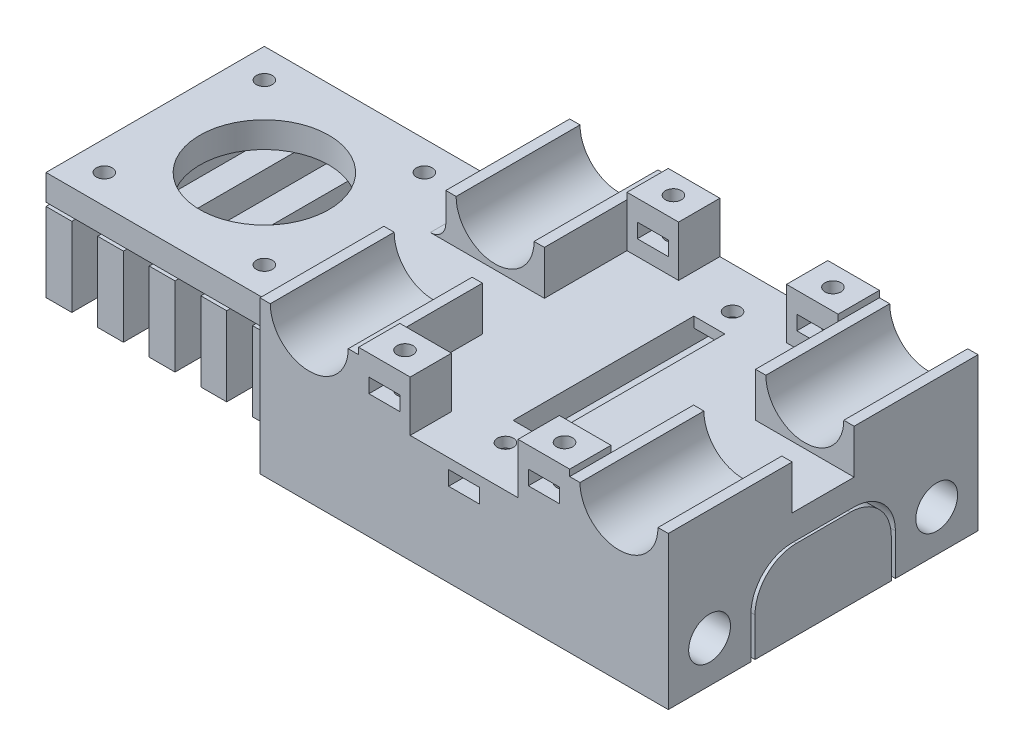
SolidWorks part; units mm, degrees
note: The reader was unsure of these and kept them because the rebuilt part matched: shared geometry of "Sketch14<3>".
ref_plane "Front Plane" through (0, 0, 0) normal (0, 0, 1) x (1, 0, 0)
ref_plane "Top Plane" through (0, 0, 0) normal (0, 1, 0) x (1, 0, 0)
ref_plane "Right Plane" through (0, 0, 0) normal (1, 0, 0) x (0, 0, -1)
sketch "Sketch1" plane through (0, 0, 0) normal (0, 1, 0) x (1, 0, 0)
  line L1 (-39.55, 30) -> (39.55, 30)
  line L2 (-39.55, 30) -> (-39.55, -30)
  line L3 (-39.55, -30) -> (39.55, -30)
  line L4 (39.55, 30) -> (39.55, -30)
  dimension "D1" = 60
  dimension "D2" = 79.1
  dimension "D3" = 39.55
  dimension "D4" = 30
extrude "Boss-Extrude1" add sketch "Sketch1" along normal blind 5
sketch "Sketch2" plane through (0, 0, 30) normal (0, 0, 1) x (1, 0, 0)
  line L0 (-39.55, 5) -> (39.55, 5) construction
  line L1 (-39.55, 5) -> (-20.45, 5)
  line L2 (-39.55, 5) -> (-39.55, 13.55)
  line L3 (-39.55, 13.55) -> (-20.45, 13.55)
  line L4 (-20.45, 5) -> (-20.45, 13.55)
  circle A0 centre (-30, 13.55) radius 7.55
  line M3 (39.55, 5) -> (-39.55, 5)
  dimension "D3" = 15.1
  dimension "D1" = 19.1
  dimension "D2" = 8.55
  dimension "D4" = 30
extrude "Boss-Extrude2" add sketch "Sketch2" against normal blind 24 contours A0 L3 L2 L4 M3
mirror "Mirror1" about plane through (0, 0, 0) normal (0, 0, 1) of "Boss-Extrude2"
mirror "Mirror2" about plane through (0, 0, 0) normal (1, 0, 0) of "Mirror1", "Boss-Extrude2"
ref_plane "Plane1" through (-30, 0, 0) normal (-1, 0, 0) x (0, 0, 1)
ref_plane "Plane2" through (-22.275, 22.275, 0) normal (-0.7071, 0.7071, 0) x (0.7071, 0.7071, 0)
sketch "Sketch3" plane through (-22.275, 22.275, 0) normal (-0.7071, 0.7071, 0) x (0.7071, 0.7071, 0)
  line L0 (-27.9661, -30) -> (-18.3848, -30) construction
  line L1 (-24.4305, -6) -> (-24.4305, 6) construction
  circle A0 centre (-27.9305, -18) radius 1.75
  dimension "D1" = 3.5
  dimension "D2" = 12
  dimension "D3" = 3.5
sketch "Sketch9" plane through (0, 0, 30) normal (0, 0, 1) x (1, 0, 0)
  line L1 (-20.45, 5) -> (-10.45, 5)
  line L2 (-20.45, 5) -> (-20.45, 14.8)
  line L3 (-20.45, 14.8) -> (-10.45, 14.8)
  line L4 (-10.45, 5) -> (-10.45, 14.8)
  line L5 (-18.45, 8) -> (-12.45, 8)
  line L6 (-18.45, 8) -> (-18.45, 10.8)
  line L7 (-18.45, 10.8) -> (-12.45, 10.8)
  line L8 (-12.45, 8) -> (-12.45, 10.8)
  line M7 (20.45, 5) -> (-20.45, 5)
  line M8 (-20.45, 5) -> (-20.45, 13.55)
  dimension "D1" = 2.8
  dimension "D2" = 6
  dimension "D3" = 2
  dimension "D4" = 2
  dimension "D5" = 4
  dimension "D6" = 3
extrude "Boss-Extrude4" add sketch "Sketch9" against normal blind 8 contours L8 L4 L3 L6 L7 M7 M8
mirror "Mirror8" about plane through (0, 0, 0) normal (1, 0, 0) of "Boss-Extrude4"
mirror "Mirror9" about plane through (0, 0, 0) normal (0, 0, 1) of "Mirror8", "Boss-Extrude4"
sketch "Sketch10" plane through (0, 14.8, 0) normal (0, 1, 0) x (1, 0, 0)
  line L0 (-20.45, -22) -> (-10.45, -22) construction
  line L1 (-10.45, -22) -> (-10.45, -30) construction
  line L2 (10.45, -22) -> (10.45, -30) construction
  line L4 (20.45, -22) -> (10.45, -22) construction
  line L5 (20.45, 22) -> (10.45, 22) construction
  line L6 (10.45, 22) -> (10.45, 30) construction
  line L7 (-10.45, 22) -> (-10.45, 30) construction
  line L8 (-20.45, 22) -> (-10.45, 22) construction
  circle A0 centre (-15.45, 26) radius 1.55
  circle A1 centre (15.45, 26) radius 1.55
  circle A2 centre (15.45, -26) radius 1.55
  circle A3 centre (-15.45, -26) radius 1.55
  point P21 (-10.45, 26)
  dimension "D1" = 3.1
  dimension "D2" = 4
  dimension "D3" = 5
  dimension "D4" = 5
  dimension "D5" = 4
  dimension "D6" = 4
  dimension "D7" = 5
  dimension "D8" = 5
  dimension "D9" = 4
extrude "Cut-Extrude6" cut sketch "Sketch10" against normal through all
sketch "Sketch11" plane through (0, 0, 0) normal (0, -1, 0) x (1, 0, 0)
  line L0 (-39.55, -30) -> (-39.55, 30) construction
  line L1 (-39.55, 30) -> (39.55, 30)
  line L2 (-39.55, 30) -> (-39.55, 14)
  line L3 (-39.55, 14) -> (39.55, 14)
  line L4 (39.55, 30) -> (39.55, 14)
  line L5 (39.55, 30) -> (39.55, -30) construction
  line L6 (-39.55, 30) -> (39.55, 30) construction
  line L7 (-39.55, -14) -> (39.55, -14)
  line L8 (-39.55, -14) -> (-39.55, -30)
  line L9 (-39.55, -30) -> (39.55, -30)
  line L10 (39.55, -14) -> (39.55, -30)
  line L11 (39.55, -30) -> (-39.55, -30) construction
  dimension "D1" = 16
  dimension "D2" = 16
  dimension "D3" = 0
  dimension "D4" = 0
extrude "Boss-Extrude5" add sketch "Sketch11" along normal blind 16
sketch "Sketch12" plane through (39.55, 0, 0) normal (1, 0, 0) x (0, 0, -1)
  line L0 (-30, 13.55) -> (-30, -16) construction
  line L1 (30, 13.55) -> (30, -16) construction
  circle A0 centre (-22, -8) radius 4.05
  circle A1 centre (22, -8) radius 4.05
  dimension "D1" = 8.1
  dimension "D2" = 8
  dimension "D3" = 8
extrude "Cut-Extrude7" cut sketch "Sketch12" against normal through all
sketch "Sketch13" plane through (0, 0, -30) normal (0, 0, -1) x (-1, 0, 0)
  line L0 (-10.45, 5) -> (10.45, 5) construction
  line L1 (-3, 3) -> (3, 3)
  line L2 (-3, 3) -> (-3, 0.2)
  line L3 (-3, 0.2) -> (3, 0.2)
  line L4 (3, 3) -> (3, 0.2)
  line L5 (-3, 3) -> (3, 0.2) construction
  line L6 (-3, 0.2) -> (3, 3) construction
  point P0 (0, 1.6)
  dimension "D1" = 6
  dimension "D2" = 2.8
  dimension "D3" = 2
extrude "Cut-Extrude8" cut sketch "Sketch13" against normal through all
sketch "Sketch14" plane through (0, 5, 0) normal (0, 1, 0) x (1, 0, 0)
  line L0 (10.45, 30) -> (-10.45, 30) construction
  line L1 (-10.45, -30) -> (10.45, -30) construction
  line L3 (-3, 17.5) -> (3, 17.5)
  line L4 (-3, 17.5) -> (-3, -17.5)
  line L5 (-3, -17.5) -> (3, -17.5)
  line L6 (3, 17.5) -> (3, -17.5)
  line L7 (-3, 17.5) -> (3, -17.5) construction
  line L8 (-3, -17.5) -> (3, 17.5) construction
  circle A0 centre (0, 22) radius 1.55
  circle A1 centre (0, -22) radius 1.55
  point P8 (0, 0)
  dimension "D1" = 3.1
  dimension "D2" = 8
  dimension "D3" = 8
  dimension "D4" = 6
  dimension "D5" = 35
extrude "Cut-Extrude9" cut sketch "Sketch14" against normal blind 10 contours A1 | A0
extrude "Cut-Extrude10" cut sketch "Sketch14<3>" against normal up to surface (4.8 mm away) contours L6 L3 L4 L5 up to face at (0, 0.2, -23.55)
sketch "Sketch14<3>" plane through (0, 5, 0) normal (0, 1, 0) x (1, 0, 0) same geometry as "Sketch14"
fillet "Fillet1" radius 8 2 edges at (0, 0, -14)
fillet "Fillet2" [suppressed] radius 8
sketch "Sketch15" plane through (0, 0, 0) normal (0, -1, 0) x (1, 0, 0)
  line L0 (-39.55, 6) -> (-39.55, 30) construction
  line L1 (-39.55, 21.15) -> (-89.85, 21.15)
  line L2 (-39.55, 21.15) -> (-39.55, -21.15)
  line L3 (-39.55, -21.15) -> (-89.85, -21.15)
  line L4 (-89.85, 21.15) -> (-89.85, -21.15)
  line L6 (-84.2, 15.5) -> (-53.2, 15.5)
  line L7 (-84.2, 15.5) -> (-84.2, -15.5)
  line L8 (-84.2, -15.5) -> (-53.2, -15.5)
  line L9 (-53.2, 15.5) -> (-53.2, -15.5)
  line L10 (-84.2, 15.5) -> (-53.2, -15.5) construction
  line L11 (-84.2, -15.5) -> (-53.2, 15.5) construction
  circle A0 centre (-84.2, 15.5) radius 1.55
  circle A1 centre (-53.2, 15.5) radius 1.55
  circle A2 centre (-53.2, -15.5) radius 1.55
  circle A3 centre (-84.2, -15.5) radius 1.55
  circle A4 centre (-68.7, 0) radius 12.5
  point P6 (-68.7, 0)
  line M1 (-39.55, 6) -> (-39.55, -6)
  dimension "D7" = 3.1
  dimension "D8" = 25
  dimension "D1" = 50.3
  dimension "D2" = 42.3
  dimension "D3" = 21.15
  dimension "D4" = 31
  dimension "D5" = 31
  dimension "D6" = 21.15
extrude "Boss-Extrude6" add sketch "Sketch15" against normal blind 5 contours L1 L4 L3 L2 A3 L7 A0 L6 A1 L9 A2 L8 M1 | A3 L8 A2 L9 A1 L6 A0 L7 A4
fillet "Fillet3" radius 3 1 edges
ref_plane "Plane3" through (0, -0.7, 0) normal (0, -1, 0) x (-1, 0, 0)
sketch "Sketch16" plane through (0, -0.7, 0) normal (0, -1, 0) x (-1, 0, 0)
  line L0 (39.55, -21.15) -> (89.85, -21.15) construction
  line L1 (89.85, 21.15) -> (84.85, 21.15)
  line L2 (89.85, 21.15) -> (89.85, -21.15)
  line L3 (89.85, -21.15) -> (84.85, -21.15)
  line L4 (84.85, 21.15) -> (84.85, -21.15)
  line L5 (79.85, 21.15) -> (74.85, 21.15)
  line L6 (79.85, 21.15) -> (79.85, -21.15)
  line L7 (79.85, -21.15) -> (74.85, -21.15)
  line L8 (74.85, 21.15) -> (74.85, -21.15)
  line L9 (69.85, 21.15) -> (64.85, 21.15)
  line L10 (69.85, 21.15) -> (69.85, -21.15)
  line L11 (69.85, -21.15) -> (64.85, -21.15)
  line L12 (64.85, 21.15) -> (64.85, -21.15)
  line L13 (59.85, 21.15) -> (54.85, 21.15)
  line L14 (59.85, 21.15) -> (59.85, -21.15)
  line L15 (59.85, -21.15) -> (54.85, -21.15)
  line L16 (54.85, 21.15) -> (54.85, -21.15)
  line L17 (49.85, 21.15) -> (44.85, 21.15)
  line L18 (49.85, 21.15) -> (49.85, -21.15)
  line L19 (49.85, -21.15) -> (44.85, -21.15)
  line L20 (44.85, 21.15) -> (44.85, -21.15)
  dimension "D1" = 5
  dimension "D2" = 5
extrude "Boss-Extrude7" add sketch "Sketch16" along normal up to surface (15.3 mm away) separate body up to face at (0, -16, -22)
sketch "Sketch17" plane through (39.55, 0, 0) normal (1, 0, 0) x (0, 0, -1)
  line L0 (21.15, -16) -> (-21.15, -16) construction
  line L1 (-13.2, -16) -> (13.2, -16)
  line L2 (-13.2, -16) -> (-13.2, -8.5)
  line L3 (-5.2, -0.5) -> (5.2, -0.5)
  line L4 (13.2, -16) -> (13.2, -8.5)
  line L5 (-6, 0) -> (6, 0) construction
  line L6 (-14, -16) -> (-14, -8) construction
  line L7 (14, -16) -> (14, -8) construction
  arc A0 (13.2, -8.5) -> (5.2, -0.5) centre (5.2, -8.5) ccw
  arc A1 (-13.2, -8.5) -> (-5.2, -0.5) centre (-5.2, -8.5) cw
  dimension "D4" = 8
  dimension "D1" = 0.5
  dimension "D2" = 0.8
  dimension "D3" = 0.8
extrude "Boss-Extrude8" add sketch "Sketch17" against normal blind 5 separate body
pattern_linear "LPattern1" count 5 spacing 18.5 along (-1, 0, 0) of "Boss-Extrude8"
